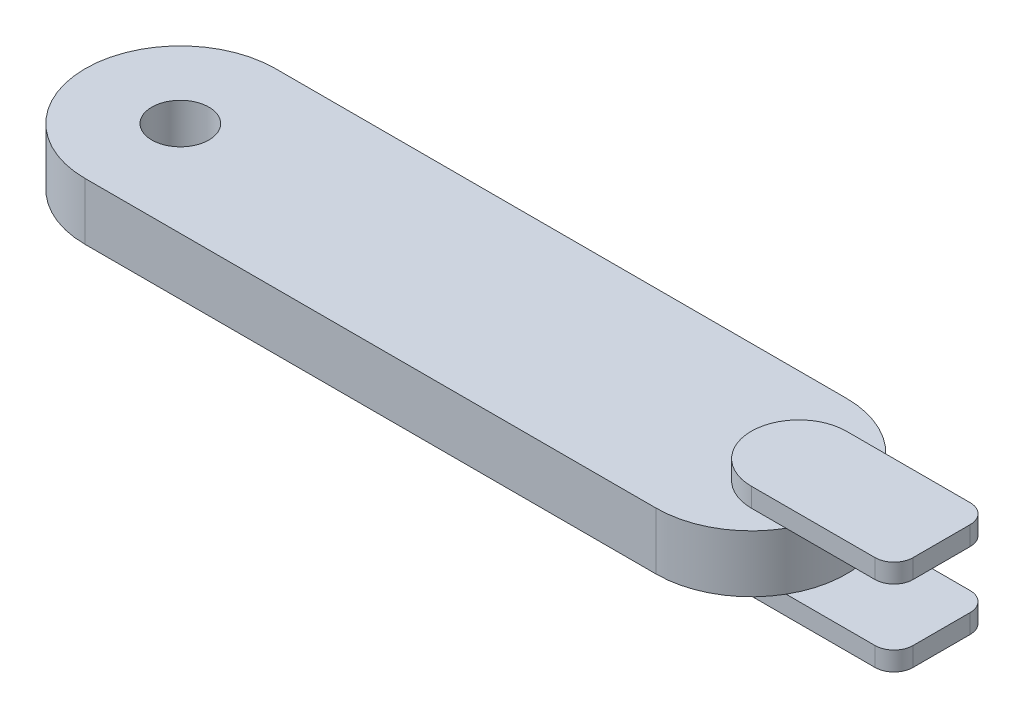
SolidWorks part; units mm, degrees
ref_plane "Front Plane" through (0, 0, 0) normal (0, 0, 1) x (1, 0, 0)
ref_plane "Top Plane" through (0, 0, 0) normal (0, 1, 0) x (1, 0, 0)
ref_plane "Right Plane" through (0, 0, 0) normal (1, 0, 0) x (0, 0, -1)
sketch "Sketch2" plane through (0, 0, 0) normal (0, 1, 0) x (1, 0, 0)
  line L0 (0, 0) -> (30, 0) construction
  line L1 (0, 5) -> (30, 5)
  line L2 (0, -5) -> (30, -5)
  arc A0 (0, 5) -> (0, -5) centre (0, 0) ccw
  arc A1 (30, -5) -> (30, 5) centre (30, 0) ccw
  point P3 (15, 0)
  dimension "D2" = 5
  dimension "D1" = 30
extrude "Boss-Extrude1" add sketch "Sketch2" along normal blind 3
sketch "Sketch5" plane through (0, 0, 0) normal (0, 0, 1) x (1, 0, 0)
  line L1 (30, 3) -> (40, 3)
  line L2 (30, 3) -> (30, 4)
  line L3 (30, 4) -> (40, 4)
  line L4 (40, 3) -> (40, 4)
  line L5 (30, 0) -> (40, 0)
  line L6 (30, 0) -> (30, -1)
  line L7 (30, -1) -> (40, -1)
  line L8 (40, 0) -> (40, -1)
  dimension "D1" = 10
  dimension "D2" = 1
extrude "Boss-Extrude2" add sketch "Sketch5" along normal mid plane 5
fillet "Fillet1" radius 2.5 4 edges at (30, -0.5, 2.5) (30, -0.5, -2.5) (30, 3.5, -2.5) (30, 3.5, 2.5)
fillet "Fillet2" radius 1 4 edges at (40, -0.5, -2.5) (40, -0.5, 2.5) (40, 3.5, 2.5) (40, 3.5, -2.5)
sketch "Sketch6" plane through (0, 3, 0) normal (0, 1, 0) x (1, 0, 0)
  circle A0 centre (0, 0) radius 1.5
  dimension "D1" = 3
extrude "Cut-Extrude1" cut sketch "Sketch6" against normal through all
